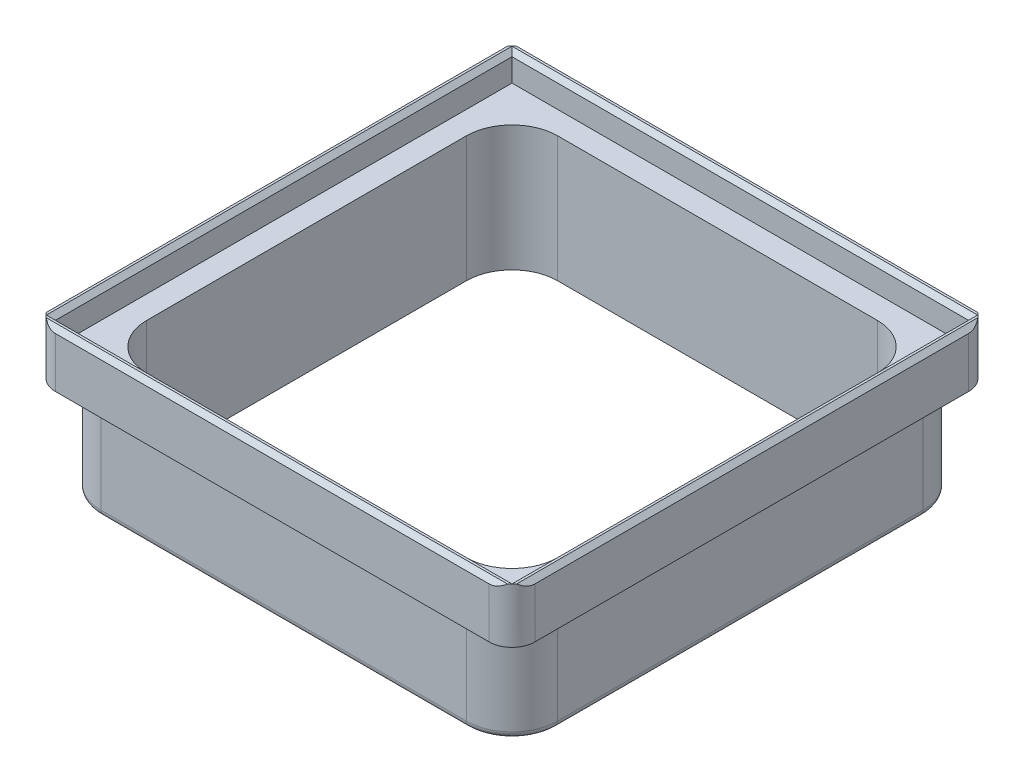
SolidWorks part; units mm, degrees
ref_plane "Front Plane" through (0, 0, 0) normal (0, 0, 1) x (1, 0, 0)
ref_plane "Top Plane" through (0, 0, 0) normal (0, 1, 0) x (1, 0, 0)
ref_plane "Right Plane" through (0, 0, 0) normal (1, 0, 0) x (0, 0, -1)
sketch "Sketch1" plane through (0, 0, 0) normal (0, 1, 0) x (1, 0, 0)
  line L1 (-100, 100) -> (100, 100)
  line L2 (-100, 100) -> (-100, -100)
  line L3 (-100, -100) -> (100, -100)
  line L4 (100, 100) -> (100, -100)
  line L5 (-100, 100) -> (100, -100) construction
  line L6 (-100, -100) -> (100, 100) construction
  point P0 (0, 0)
  dimension "D1" = 200
extrude "Boss-Extrude1" add sketch "Sketch1" against normal blind 55
fillet "Fillet1" radius 20 4 edges at (100, -27.5, -100) (-100, -27.5, -100) (-100, -27.5, 100) (100, -27.5, 100)
sketch "Sketch2" plane through (0, 0, 0) normal (0, 1, 0) x (1, 0, 0)
  line L1 (-100, -100) -> (100, -100)
  line L2 (-100, -100) -> (-100, 100)
  line L3 (-100, 100) -> (100, 100)
  line L4 (100, -100) -> (100, 100)
  line L5 (-100, -100) -> (100, 100) construction
  line L6 (-100, 100) -> (100, -100) construction
  line L8 (-100, 100) -> (-100, 105) construction
  line L9 (-105, 105) -> (105, 105)
  line L10 (-105, 105) -> (-105, -105)
  line L11 (-105, -105) -> (105, -105)
  line L12 (105, 105) -> (105, -105)
  line L13 (-105, 105) -> (105, -105) construction
  line L14 (-105, -105) -> (105, 105) construction
  line L15 (-100, 100) -> (-105, 100) construction
  point P0 (0, 0)
  point P11 (0, 0)
  dimension "D1" = 5
  dimension "D2" = 200
  dimension "D3" = 200
extrude "Boss-Extrude2" add sketch "Sketch2" along normal blind 12 separate body
sketch "Sketch3" plane through (0, 0, 0) normal (0, 1, 0) x (1, 0, 0)
  line L1 (-105, -105) -> (105, -105)
  line L2 (-105, -105) -> (-105, 105)
  line L3 (-105, 105) -> (105, 105)
  line L4 (105, -105) -> (105, 105)
  line L5 (-105, -105) -> (105, 105) construction
  line L6 (-105, 105) -> (105, -105) construction
  point P0 (0, 0)
extrude "Boss-Extrude3" add sketch "Sketch3" against normal blind 12
combine bodies "Combine2" operation type add bodies to combine 102 103
sketch "Sketch5" plane through (0, 0, 0) normal (0, 1, 0) x (1, 0, 0)
  line L0 (90, 100) -> (90, 90) construction
  line L1 (-90, -90) -> (90, -90)
  line L2 (-90, -90) -> (-90, 90)
  line L3 (-90, 90) -> (90, 90)
  line L4 (90, -90) -> (90, 90)
  line L5 (-90, -90) -> (90, 90) construction
  line L6 (-90, 90) -> (90, -90) construction
  line L7 (100, 100) -> (-100, 100) construction
  line L8 (90, 90) -> (100, 90) construction
  line L9 (100, -100) -> (100, 100) construction
  point P0 (0, 0)
  dimension "D1" = 10
extrude "Cut-Extrude1" cut sketch "Sketch5" against normal through all both and the other way through all
chamfer "Chamfer1" distance 2 angle 45 8 edges at (-100, 12, 0) (0, 12, 100) (100, 12, 0) (0, 12, -100) (0, 12, 105) (-105, 12, 0) (0, 12, -105) (105, 12, 0)
fillet "Fillet2" radius 10 4 edges at (105, -1, 105) (-105, -1, 105) (-105, -1, -105) (105, -1, -105)
fillet "Fillet3" radius 3 16 edges at (94.1421, -55, -94.1421) (100, -55, 0) (94.1421, -55, 94.1421) (0, -55, 100) (-94.1421, -55, 94.1421) (-100, -55, 0) (-94.1421, -55, -94.1421) (94.1421, -12, -94.1421) (100, -12, 0) (94.1421, -12, 94.1421) (0, -12, 100) (-94.1421, -12, 94.1421) (-100, -12, 0) (-94.1421, -12, -94.1421) (0, -55, -100) (0, -12, -100)
fillet "Fillet4" radius 20 4 edges at (90, -27.5, -90) (90, -27.5, 90) (-90, -27.5, 90) (-90, -27.5, -90)
